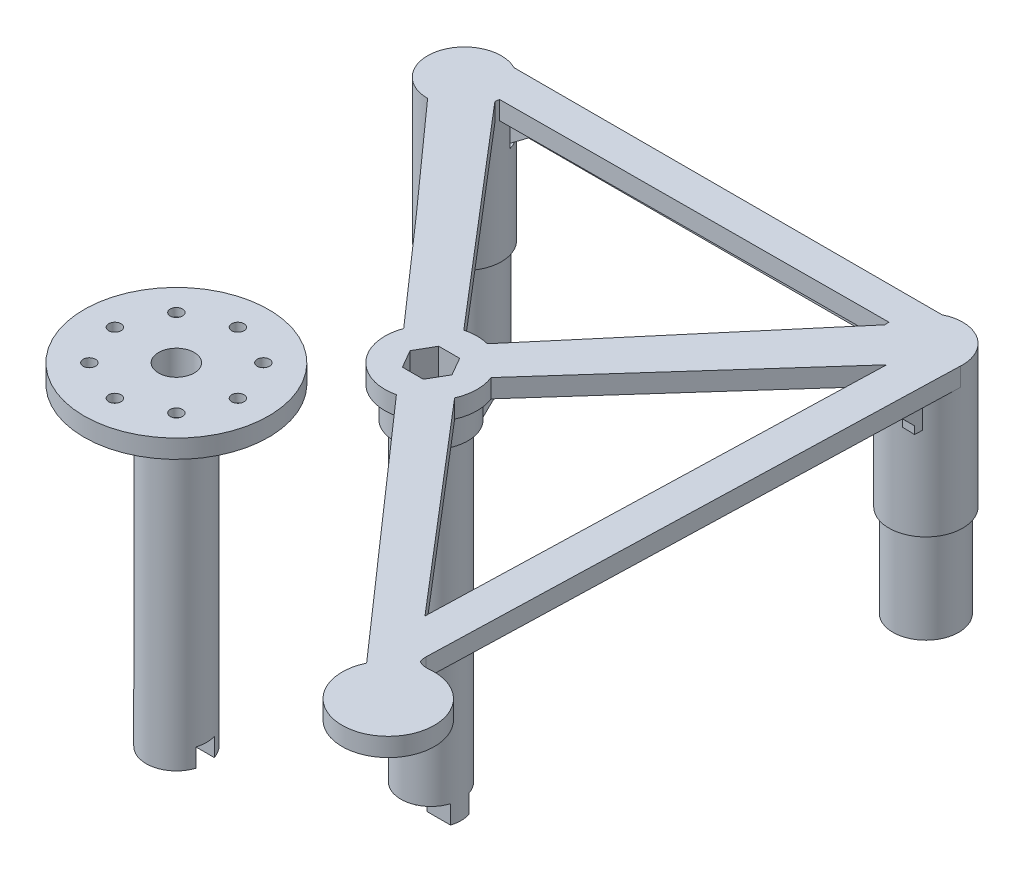
SolidWorks part; units mm, degrees
ref_plane "前视基准面" through (0, 0, 0) normal (0, 0, 1) x (1, 0, 0)
ref_plane "上视基准面" through (0, 0, 0) normal (0, 1, 0) x (1, 0, 0)
ref_plane "右视基准面" through (0, 0, 0) normal (1, 0, 0) x (0, 0, -1)
sketch "草图1" plane through (0, 0, 0) normal (0, 1, 0) x (1, 0, 0)
  line L1 (-18.6554, 0) -> (18.8446, -42.931)
  line L2 (18.8446, -42.931) -> (56.3446, 0)
  line L3 (-18.6554, 0) -> (56.3446, 0)
  dimension "D4" = 75
extrude "凸台-拉伸1" add sketch "草图1" along normal blind 3
sketch "草图2" plane through (0, 3, 0) normal (0, 1, 0) x (1, 0, 0)
  circle A0 centre (56.3446, 0) radius 5.35
  circle A1 centre (-18.6554, 0) radius 5.35
  dimension "D1" = 10.7
  dimension "D2" = 10.7
extrude "凸台-拉伸2" add sketch "草图2" against normal blind 23
sketch "草图3" plane through (0, 0, 0) normal (0, -1, 0) x (1, 0, 0)
  line L6 (8.6327, 17.5594) -> (1.1561, 9)
  line L7 (1.1561, 9) -> (33.7591, 9)
  line L8 (8.6327, 17.5594) -> (18.8446, 29.2503)
  line L9 (18.8446, 29.2503) -> (29.0566, 17.5594)
  line L10 (29.0566, 17.5594) -> (36.5332, 9)
  line L11 (36.5332, 9) -> (33.7591, 9)
  dimension "D4" = 26.8879
  dimension "D5" = 26.8879
  dimension "D6" = 35.3771
extrude "切除-拉伸1" cut sketch "草图3" against normal blind 3
sketch "草图4" plane through (0, 0, 0) normal (0, -1, 0) x (1, 0, 0)
  circle A0 centre (18.8446, 42.931) radius 5
  dimension "D1" = 10
extrude "凸台-拉伸3" add sketch "草图4" along normal blind 100
sketch "草图5" plane through (0, 0, 0) normal (0, 1, 0) x (1, 0, 0)
  circle A0 centre (18.8446, -42.931) radius 5
extrude "凸台-拉伸4" add sketch "草图5" along normal blind 3
sketch "草图6" plane through (0, -20, 0) normal (0, -1, 0) x (1, 0, 0)
  circle A0 centre (56.3446, 0) radius 5.35
extrude "凸台-拉伸5" add sketch "草图6" along normal blind 5
sketch "草图7" plane through (0, -20, 0) normal (0, -1, 0) x (1, 0, 0)
  circle A0 centre (-18.6554, 0) radius 5.35
extrude "凸台-拉伸6" add sketch "草图7" along normal blind 5
sketch "草图8" plane through (0, 3, 0) normal (0, 1, 0) x (1, 0, 0)
  line L0 (-18.6554, 5.35) -> (56.3446, 5.35)
  line L1 (56.3446, 5.35) -> (56.3446, -5.35)
  line L2 (56.3446, -5.35) -> (-18.6554, -5.35)
  line L3 (-18.6554, -5.35) -> (-18.6554, 5.35)
  arc A1 (52.8251, -4.0293) -> (50.9946, 0) centre (56.3446, 0) ccw construction
  arc A2 (-13.3054, 0) -> (-15.1358, -4.0293) centre (-18.6554, 0) ccw construction
  circle A3 centre (-18.6554, 0) radius 5.35 construction
extrude "凸台-拉伸7" add sketch "草图8" against normal blind 3
sketch "草图9" plane through (0, 3, 0) normal (0, 1, 0) x (1, 0, 0)
  line L0 (61.6946, 0) -> (18.8446, -47.931)
  line L1 (18.8446, -47.931) -> (-24.0054, 0)
  line L2 (-24.0054, 0) -> (61.6946, 0)
  arc A0 (56.3446, -5.35) -> (56.3446, 5.35) centre (56.3446, 0) ccw construction
  arc A1 (15.5553, -39.1653) -> (22.134, -39.1653) centre (18.8446, -42.931) ccw construction
  arc A2 (-18.6554, 5.35) -> (-18.6554, -5.35) centre (-18.6554, 0) ccw construction
extrude "凸台-拉伸8" add sketch "草图9" against normal blind 3
sketch "草图10" plane through (0, 0, 0) normal (0, -1, 0) x (1, 0, 0)
  line L0 (18.8446, 37.931) -> (-13.3137, 0.299)
  line L1 (-13.3137, 0.299) -> (50.9946, 0)
  line L2 (50.9946, 0) -> (18.8446, 37.931)
  arc A0 (13.8759, 42.373) -> (23.8134, 42.373) centre (18.8446, 42.931) ccw construction
  arc A1 (-18.6554, -5.35) -> (-19.2524, 5.3166) centre (-18.6554, 0) ccw construction
  circle A2 centre (56.3446, 0) radius 5.35 construction
  arc A3 (56.9416, 5.3166) -> (56.3446, -5.35) centre (56.3446, 0) ccw construction
extrude "切除-拉伸2" cut sketch "草图10" against normal blind 3
sketch "草图12" plane through (0, 3, 0) normal (0, 1, 0) x (1, 0, 0)
  circle A0 centre (-18.6554, 0) radius 6
  circle A1 centre (56.3446, 0) radius 6
  dimension "D1" = 12
  dimension "D2" = 12
extrude "凸台-拉伸10" add sketch "草图12" against normal blind 13
sketch "草图13" plane through (0, -25, 0) normal (0, -1, 0) x (1, 0, 0)
  circle A0 centre (-18.6554, 0) radius 3
  circle A1 centre (56.3446, 0) radius 3
  dimension "D1" = 6
  dimension "D2" = 6
extrude "切除-拉伸3" cut sketch "草图13" against normal blind 23
sketch "草图14" plane through (0, -100, 0) normal (0, -1, 0) x (1, 0, 0)
  circle A0 centre (18.8446, 42.931) radius 3.125
  dimension "D1" = 6.25
extrude "切除-拉伸5" cut sketch "草图14" against normal blind 100
sketch "草图15" plane through (0, -10, 0) normal (0, -1, 0) x (1, 0, 0)
  circle A0 centre (56.3446, 0) radius 5.35
  circle A1 centre (56.3446, 0) radius 6
extrude "凸台-拉伸11" add sketch "草图15" along normal blind 5
sketch "草图16" plane through (0, -10, 0) normal (0, -1, 0) x (1, 0, 0)
  circle A0 centre (-18.6554, 0) radius 3
  circle A1 centre (-18.6554, 0) radius 6
extrude "凸台-拉伸12" add sketch "草图16" along normal blind 5
sketch "草图17" plane through (0, -25, 0) normal (0, -1, 0) x (1, 0, 0)
  circle A0 centre (-18.6554, 0) radius 3
  circle A1 centre (-18.6554, 0) radius 5.35
extrude "凸台-拉伸13" add sketch "草图17" along normal blind 5
sketch "草图18" plane through (0, -25, 0) normal (0, -1, 0) x (1, 0, 0)
  circle A0 centre (56.3446, 0) radius 3
  circle A1 centre (56.3446, 0) radius 5.35
extrude "凸台-拉伸14" add sketch "草图18" along normal blind 5
sketch "草图20" plane through (0, -15, 0) normal (0, -1, 0) x (1, 0, 0)
  circle A0 centre (-18.6554, 0) radius 5.35
  circle A1 centre (-18.6554, 0) radius 6
extrude "凸台-拉伸15" add sketch "草图20" along normal blind 5
sketch "草图21" plane through (0, -15, 0) normal (0, -1, 0) x (1, 0, 0)
  circle A0 centre (56.3446, 0) radius 5.35
  circle A1 centre (56.3446, 0) radius 6
extrude "凸台-拉伸16" add sketch "草图21" along normal blind 5
sketch "草图22" plane through (0, -30, 0) normal (0, -1, 0) x (1, 0, 0)
  circle A0 centre (-18.6554, 0) radius 3
  circle A1 centre (-18.6554, 0) radius 5.35
extrude "凸台-拉伸17" add sketch "草图22" along normal blind 5
sketch "草图23" plane through (0, -30, 0) normal (0, -1, 0) x (1, 0, 0)
  circle A0 centre (56.3446, 0) radius 3
  circle A1 centre (56.3446, 0) radius 5.35
extrude "凸台-拉伸18" add sketch "草图23" along normal blind 5
sketch "草图25" plane through (0, 3, 0) normal (0, 1, 0) x (1, 0, 0)
  circle A0 centre (18.8446, -42.931) radius 7.5
  dimension "D1" = 15
extrude "凸台-拉伸20" add sketch "草图25" against normal blind 3
sketch "草图28" plane through (0, 3, 0) normal (0, 1, 0) x (1, 0, 0)
  line L1 (-3.3796, -23.0714) -> (2.0936, -18.3287)
  line L2 (-3.3796, -23.0714) -> (64.3216, -100.0268)
  line L3 (64.3216, -100.0268) -> (66.8686, -97.9101)
  line L4 (-18.6414, -6) -> (11.8821, -40.1429) construction
  line L5 (2.0936, -18.3287) -> (68.6526, -96.2167)
  line L6 (16.9224, -35.6815) -> (-12.7353, -0.9759) construction
  line L7 (68.6526, -96.2167) -> (66.8686, -97.9101)
extrude "凸台-拉伸21" add sketch "草图28" against normal blind 3
sketch "草图29" plane through (0, 3, 0) normal (0, 1, 0) x (1, 0, 0)
  line L0 (56.3446, 0) -> (53.7411, -88)
  line L1 (20.5226, -50.2409) -> (64.3216, -100.0268) construction
  line L2 (53.7411, -88) -> (59.7411, -88)
  line L3 (56.3446, 0) -> (62.3446, 0)
  line L4 (62.3446, 0) -> (59.7411, -88)
  arc A1 (56.3307, -6) -> (53.6285, 5.35) centre (56.3446, 0) ccw construction
  dimension "D2" = 6
  dimension "D3" = 88
extrude "凸台-拉伸23" add sketch "草图29" against normal blind 3
sketch "草图30" plane through (0, 3, 0) normal (0, 1, 0) x (1, 0, 0)
  circle A0 centre (62.6532, -93.6946) radius 7.5
  dimension "D1" = 15
extrude "凸台-拉伸24" add sketch "草图30" against normal blind 3
fillet "圆角1" radius 3 2 edges at (60.3876, 1.5, 86.545) (59.8043, 1.5, 85.8624)
sketch "草图31" plane through (0, 0, 0) normal (0, -1, 0) x (1, 0, 0)
  line L0 (-14.7236, -1.6282) -> (-14.7236, -3.6282)
  line L1 (-14.7236, -3.6282) -> (53.5274, -3.6282)
  line L2 (53.5274, -3.6282) -> (53.8249, -1.6282)
  line L3 (53.8249, -1.6282) -> (-14.7236, -1.6282)
  line L4 (49.6098, 80.1025) -> (51.1303, 78.8032)
  line L5 (22.3188, 45.0877) -> (51.1303, 78.8032)
  line L6 (49.6098, 80.1025) -> (20.7983, 46.387)
  line L7 (-15.3496, 4.0864) -> (-13.8291, 2.7871)
  line L8 (20.3259, 39.1868) -> (51.8689, 1.9719)
  line L9 (20.3259, 39.1868) -> (21.8516, 40.4799)
  line L10 (51.8689, 1.9719) -> (53.3946, 3.265)
  line L11 (21.8516, 40.4799) -> (53.3946, 3.265)
  line L12 (20.7983, 46.387) -> (22.3188, 45.0877)
  line L13 (15.5768, 40.2768) -> (17.0973, 38.9775)
  line L14 (17.0973, 38.9775) -> (-13.8291, 2.7871)
  line L15 (-15.3496, 4.0864) -> (15.5768, 40.2768)
  line L16 (56.0939, 78.8643) -> (58.3189, 3.6596)
  line L17 (58.3189, 3.6596) -> (60.3198, 3.6596)
  line L18 (60.3198, 3.6596) -> (58.093, 78.9234)
  line L19 (58.093, 78.9234) -> (56.0939, 78.8643)
  circle A0 centre (-18.6554, 0) radius 5.35 construction
  circle A1 centre (56.3446, 0) radius 3 construction
  dimension "D1" = 2
  dimension "D2" = 2
  dimension "D3" = 2
  dimension "D4" = 2
  dimension "D5" = 2
extrude "凸台-拉伸29" add sketch "草图31" along normal blind 5
sketch "草图35" plane through (0, 0, -3.6282) normal (0, 0, -1) x (-1, 0, 0)
  line L0 (13.8766, -5) -> (9.8766, -2)
  line L1 (9.8766, -2) -> (-47.5659, -2)
  line L2 (-47.5659, -2) -> (-51.5659, -5)
  line L3 (-51.5659, -5) -> (13.8766, -5)
  line L4 (13.8766, 0) -> (-51.5659, 0) construction
  dimension "D1" = 2
  dimension "D2" = 4
  dimension "D3" = 4
sketch "草图36" plane through (0, -5, 0) normal (0, -1, 0) x (1, 0, 0)
  line L0 (18.8446, -3.6282) -> (18.8446, -1.6282)
  line L1 (-9.8766, -3.6282) -> (47.5659, -3.6282) construction
  line L2 (50.5698, -1.6282) -> (-12.8805, -1.6282) construction
sweep "切除-扫描1" cut profiles "草图35" path "草图36"
sketch "草图37" plane through (60.3752, 0, 1.7863) normal (0.9996, 0, 0.0296) x (0.0296, 0, -0.9996)
  line L0 (-2.7315, -5) -> (-6.7315, -1)
  line L1 (-6.7315, -1) -> (-73.1709, -1)
  line L2 (-73.1709, -1) -> (-77.1709, -5)
  line L3 (-77.1709, -5) -> (-2.7315, -5)
  line L5 (-82.8983, 0) -> (1.4889, 0) construction
  dimension "D1" = 1
  dimension "D2" = 4
  dimension "D3" = 4
sketch "草图38" plane through (0, -5, 0) normal (0, -1, 0) x (1, 0, 0)
  line L0 (59.1937, 41.72) -> (57.1928, 41.72)
  line L1 (60.1761, 8.5148) -> (58.2113, 74.9252) construction
  line L2 (56.0939, 78.8643) -> (58.2589, 5.6864) construction
sweep "切除-扫描3" cut profiles "草图37" path "草图38"
sketch "草图39" plane through (58.3761, 0, 1.7271) normal (0.9996, 0, 0.0296) x (0.0296, 0, -0.9996)
  line L0 (-3.961, -3.8296) -> (-3.961, -5)
  line L1 (-3.961, -5) -> (-2.7315, -5)
  line L2 (-3.961, -3.8296) -> (-3.961, -3.2722)
  line L3 (-3.961, -3.2722) -> (-2.7315, -4.5017)
  line L4 (-2.7315, 0) -> (-2.7315, -5) construction
  line L5 (-2.7315, -4.5017) -> (-2.7315, -5)
extrude "凸台-拉伸31" add sketch "草图39" along normal blind 2
sketch "草图40" plane through (-10.8895, 0, 9.3056) normal (-0.7602, 0, 0.6497) x (0.6497, 0, 0.7602)
  line L0 (-5.1212, -5) -> (-3.1212, -1)
  line L2 (39.938, -5) -> (-6.1212, -5) construction
  line L3 (-3.1212, -1) -> (36.938, -1)
  line L5 (36.938, -1) -> (38.938, -5)
  line L6 (38.938, -5) -> (-5.1212, -5)
  line L7 (39.938, 0) -> (-6.1212, 0) construction
  dimension "D1" = 1
  dimension "D2" = 2
  dimension "D3" = 1
  dimension "D4" = 1
  dimension "D5" = 2
sketch "草图42" plane through (0, -5, 0) normal (0, -1, 0) x (1, 0, 0)
  line L0 (0.0951, 22.1599) -> (1.5521, 20.7864)
  line L1 (-12.9172, 6.9328) -> (13.1074, 37.387) construction
  line L2 (-13.5363, 3.1298) -> (16.6406, 38.443) construction
sweep "切除-扫描5" cut profiles "草图40" path "草图42"
sketch "草图43" plane through (31.1568, 0, 26.4083) normal (-0.7628, 0, -0.6466) x (-0.6466, 0, 0.7628)
  line L0 (14.7346, -5) -> (12.7346, -1)
  line L1 (15.7346, -5) -> (-30.8257, -5) construction
  line L2 (12.7346, -1) -> (-27.8257, -1)
  line L3 (-27.8257, -1) -> (-29.8257, -5)
  line L4 (14.7346, -5) -> (-29.8257, -5)
  line L5 (15.7346, 0) -> (-30.8257, 0) construction
  dimension "D1" = 1
  dimension "D2" = 1
  dimension "D3" = 1
  dimension "D4" = 2
  dimension "D5" = 2
sketch "草图44" plane through (0, -5, 0) normal (0, -1, 0) x (1, 0, 0)
  line L0 (36.0357, 20.6522) -> (37.4729, 22.0498)
  line L1 (22.9229, 36.1228) -> (49.1484, 5.1816) construction
  line L2 (52.36, 4.4858) -> (22.5858, 39.6138) construction
sweep "切除-扫描6" cut profiles "草图43" path "草图44"
sketch "草图46" plane through (-10.8895, 0, 9.3056) normal (-0.7602, 0, 0.6497) x (0.6497, 0, 0.7602)
  line L0 (50.8218, -5) -> (52.8218, -1)
  line L1 (93.1256, -5) -> (49.8218, -5) construction
  line L2 (52.8218, -1) -> (88.1256, -1)
  line L3 (88.1256, -1) -> (93.1256, 0)
  line L4 (93.1256, 0) -> (93.1256, -5)
  line L5 (93.1256, -5) -> (50.8218, -5)
  line L6 (93.1256, 0) -> (49.8218, 0) construction
  dimension "D1" = 1
  dimension "D2" = 1
  dimension "D3" = 2
  dimension "D4" = 5
sketch "草图47" plane through (0, -5, 0) normal (0, -1, 0) x (1, 0, 0)
  line L0 (37.0322, 62.3055) -> (35.5118, 63.6048)
  line L1 (22.9341, 45.8078) -> (51.1303, 78.8032) construction
  line L2 (23.4264, 49.4624) -> (46.3616, 76.3014) construction
sweep "切除-扫描7" cut profiles "草图46" path "草图47"
sketch "草图48" plane through (60.3752, 0, 1.7863) normal (0.9996, 0, 0.0296) x (0.0296, 0, -0.9996)
  line L0 (-73.1709, -1) -> (-77.1709, 0)
  line L1 (-77.1709, 0) -> (-77.1709, -5)
  line L2 (-73.1709, -1) -> (-77.1709, -5)
sketch "草图49" plane through (0, -1, 0) normal (0, -1, 0) x (1, 0, 0)
  line L0 (58.2113, 74.9252) -> (56.2104, 74.9252)
  line L1 (56.2104, 74.9252) -> (55.38, 74.9252)
sweep "切除-扫描8" cut profiles "草图48" path "草图49"
sketch "草图50" plane through (0, 3, 0) normal (0, 1, 0) x (1, 0, 0)
  circle A0 centre (18.8446, -42.931) radius 5.9982
extrude "凸台-拉伸32" add sketch "草图50" against normal blind 103
sketch "草图52" plane through (0, -100, 0) normal (0, -1, 0) x (1, 0, 0)
  circle A0 centre (18.8446, 42.931) radius 5.9982
  circle A1 centre (18.8446, 42.931) radius 4.9
  dimension "D1" = 9.8
extrude "切除-拉伸7" cut sketch "草图52" against normal blind 95
sketch "草图53" plane through (0, -100, 0) normal (0, -1, 0) x (1, 0, 0)
  circle A0 centre (18.8446, 42.931) radius 4.9
extrude "切除-拉伸8" cut sketch "草图53" against normal blind 44
sketch "草图54" plane through (0, -56, 0) normal (0, -1, 0) x (1, 0, 0)
  line L1 (22.0201, 42.931) -> (20.4324, 45.681)
  line L2 (20.4324, 45.681) -> (17.2569, 45.681)
  line L3 (17.2569, 45.681) -> (15.6692, 42.931)
  line L4 (15.6692, 42.931) -> (17.2569, 40.181)
  line L5 (17.2569, 40.181) -> (20.4324, 40.181)
  line L6 (20.4324, 40.181) -> (22.0201, 42.931)
  circle A0 centre (18.8446, 42.931) radius 1.5
  circle A1 centre (18.8446, 42.931) radius 2.75 construction
  dimension "D1" = 3
  dimension "D2" = 5.5
extrude "凸台-拉伸33" add sketch "草图54" along normal blind 5
sketch "草图55" plane through (0, 3, 0) normal (0, 1, 0) x (1, 0, 0)
  line L1 (22.0778, -42.931) -> (20.4612, -40.131)
  line L2 (20.4612, -40.131) -> (17.2281, -40.131)
  line L3 (17.2281, -40.131) -> (15.6115, -42.931)
  line L4 (15.6115, -42.931) -> (17.2281, -45.731)
  line L5 (17.2281, -45.731) -> (20.4612, -45.731)
  line L6 (20.4612, -45.731) -> (22.0778, -42.931)
  circle A0 centre (18.8446, -42.931) radius 2.8 construction
  dimension "D1" = 5.6
extrude "切除-拉伸9" cut sketch "草图55" against normal blind 56
sketch "草图56" plane through (0, -56, 0) normal (0, -1, 0) x (1, 0, 0)
  circle A0 centre (18.8446, 42.931) radius 1.5
extrude "切除-拉伸10" cut sketch "草图56" against normal blind 6
sketch "草图57" plane through (0, 0, 0) normal (0, 1, 0) x (1, 0, 0)
  circle A1 centre (-1.8509, -63.6265) radius 15
  dimension "D1" = 30
extrude "凸台-拉伸34" add sketch "草图57" along normal blind 3 separate body
sketch "草图58" plane through (0, 0, 0) normal (0, -1, 0) x (1, 0, 0)
  circle A0 centre (-1.8509, 63.6265) radius 4.9
  dimension "D1" = 9.8
extrude "凸台-拉伸35" add sketch "草图58" along normal blind 51
sketch "草图59" plane through (0, -51, 0) normal (0, -1, 0) x (1, 0, 0)
  line L1 (1.3246, 63.6265) -> (-0.2631, 66.3765)
  line L2 (-0.2631, 66.3765) -> (-3.4386, 66.3765)
  line L3 (-3.4386, 66.3765) -> (-5.0263, 63.6265)
  line L4 (-5.0263, 63.6265) -> (-3.4386, 60.8765)
  line L5 (-3.4386, 60.8765) -> (-0.2631, 60.8765)
  line L6 (-0.2631, 60.8765) -> (1.3246, 63.6265)
  circle A0 centre (-1.8509, 63.6265) radius 2.75 construction
  dimension "D1" = 5.5
extrude "切除-拉伸11" cut sketch "草图59" against normal blind 5
sketch "草图60" plane through (0, 3, 0) normal (0, 1, 0) x (1, 0, 0)
  circle A0 centre (-1.8509, -63.6265) radius 2.75
  dimension "D1" = 5.5
extrude "切除-拉伸12" cut sketch "草图60" against normal blind 46
sketch "草图61" plane through (0, -46, 0) normal (0, -1, 0) x (1, 0, 0)
  circle A0 centre (-1.8509, 63.6265) radius 1.5
  dimension "D1" = 3
extrude "切除-拉伸13" cut sketch "草图61" against normal blind 9
sketch "草图62" plane through (0, 0, 0) normal (0, -1, 0) x (1, 0, 0)
  line L4 (10.5163, 63.6265) -> (9.3327, 65.6765)
  line L5 (9.3327, 65.6765) -> (6.9656, 65.6765)
  line L6 (6.9656, 65.6765) -> (5.782, 63.6265)
  line L7 (5.782, 63.6265) -> (6.9656, 61.5765)
  line L8 (6.9656, 61.5765) -> (9.3327, 61.5765)
  line L9 (9.3327, 61.5765) -> (10.5163, 63.6265)
  circle A1 centre (8.1491, 63.6265) radius 2.05 construction
  dimension "D2" = 4.1
extrude "切除-拉伸14" cut sketch "草图62" against normal blind 1.65
sketch "草图63" plane through (0, 1.65, 0) normal (0, -1, 0) x (1, 0, 0)
  circle A0 centre (8.1491, 63.6265) radius 1
  dimension "D1" = 2
extrude "切除-拉伸15" cut sketch "草图63" against normal blind 1.5
pattern_circular "阵列(圆周)1" count 8 over 360 about axis through (-1.8509, -51, 63.6265) along (0, 1, 0) of "切除-拉伸14", "切除-拉伸15"
sketch "草图64" plane through (0, -61, 0) normal (0, -1, 0) x (1, 0, 0)
  circle A0 centre (18.8446, 42.931) radius 3.1754
extrude "切除-拉伸17" cut sketch "草图64" against normal blind 5
sketch "草图65" plane through (0, 3, 0) normal (0, 1, 0) x (1, 0, 0)
  line L1 (22.251, -42.931) -> (20.5478, -39.981)
  line L2 (20.5478, -39.981) -> (17.1415, -39.981)
  line L3 (17.1415, -39.981) -> (15.4383, -42.931)
  line L4 (15.4383, -42.931) -> (17.1415, -45.881)
  line L5 (17.1415, -45.881) -> (20.5478, -45.881)
  line L6 (20.5478, -45.881) -> (22.251, -42.931)
  circle A0 centre (18.8446, -42.931) radius 2.95 construction
  dimension "D1" = 5.9
extrude "切除-拉伸18" cut sketch "草图65" against normal blind 56
fillet "圆角2" radius 1 6 edges at (16.2899, -53, 41.456) (16.2899, -53, 44.406) (18.8446, -53, 45.881) (21.3994, -53, 44.406) (21.3994, -53, 41.456) (18.8446, -53, 39.981)
sketch "草图66" plane through (0, -51, 0) normal (0, -1, 0) x (1, 0, 0)
  line L1 (1.3246, 63.6265) -> (-0.2631, 66.3765)
  line L2 (-0.2631, 66.3765) -> (-3.4386, 66.3765)
  line L3 (-3.4386, 66.3765) -> (-5.0263, 63.6265)
  line L4 (-5.0263, 63.6265) -> (-3.4386, 60.8765)
  line L5 (-3.4386, 60.8765) -> (-0.2631, 60.8765)
  line L6 (-0.2631, 60.8765) -> (1.3246, 63.6265)
  circle A0 centre (-1.8509, 63.6265) radius 2.75 construction
extrude "凸台-拉伸36" add sketch "草图66" against normal blind 5
sketch "草图67" plane through (0, -51, 0) normal (0, -1, 0) x (1, 0, 0)
  circle A0 centre (-1.8509, 63.6265) radius 1.5
extrude "切除-拉伸19" cut sketch "草图67" against normal blind 5
fillet "圆角3" radius 1 1 edges at (-1.8509, -43, 66.3765)
sketch "草图68" plane through (0, -56, 0) normal (0, -1, 0) x (1, 0, 0)
  line L0 (17.9735, 41.4222) -> (13.9446, 41.431)
  line L2 (19.7158, 41.4222) -> (23.7446, 41.431)
  line L3 (13.9446, 44.431) -> (17.9735, 44.4398)
  line L4 (13.9446, 44.431) -> (15.6975, 48.0373)
  line L5 (19.7158, 44.4398) -> (23.7446, 44.431)
  line L6 (15.6975, 48.0373) -> (21.9917, 48.0373)
  line L7 (21.9917, 48.0373) -> (23.7446, 44.431)
  line L8 (23.7446, 41.431) -> (21.6473, 37.6278)
  line L9 (21.6473, 37.6278) -> (15.8637, 37.534)
  line L10 (20.5869, 42.931) -> (19.7158, 44.4398)
  line L11 (15.8637, 37.534) -> (13.9446, 41.431)
  line L12 (17.9735, 44.4398) -> (17.1024, 42.931)
  line L13 (17.1024, 42.931) -> (17.9735, 41.4222)
  line L15 (19.7158, 41.4222) -> (20.5869, 42.931)
  line L21 (17.9735, 41.4222) -> (19.7158, 41.4222) [skipped]
  line L22 (19.7158, 44.4398) -> (17.9735, 44.4398) [skipped]
  circle A3 centre (18.8446, 42.931) radius 1.5088 construction
  arc A4 (23.3281, 46.9155) -> (15.1566, 38.2006) centre (18.8446, 42.931) ccw construction
  arc A5 (22.1322, 47.948) -> (14.4015, 38.9014) centre (18.8446, 42.931) ccw construction
sketch "草图69" plane through (0, -56, 0) normal (0, -1, 0) x (1, 0, 0)
  circle A0 centre (18.8446, 42.931) radius 4.9
extrude "凸台-拉伸37" add sketch "草图69" along normal blind 3
extrude "切除-拉伸20" cut sketch "草图68" along normal blind 3
sketch "草图70" plane through (0, -51, 0) normal (0, -1, 0) x (1, 0, 0)
  line L0 (-2.7169, 65.1265) -> (-0.9848, 65.1265)
  line L1 (-0.9848, 65.1265) -> (3.2201, 65.1265)
  line L3 (-0.9848, 62.1265) -> (-2.7169, 62.1265)
  line L8 (3.2201, 65.1265) -> (3.2201, 62.1265)
  line L9 (3.2201, 62.1265) -> (-0.9848, 62.1265)
  line L10 (-2.7169, 62.1265) -> (-7.4797, 62.1265)
  line L11 (-7.4797, 62.1265) -> (-7.4797, 65.1265)
  line L12 (-7.4797, 65.1265) -> (-2.7169, 65.1265)
extrude "切除-拉伸21" cut sketch "草图70" against normal blind 3
sketch "草图71" plane through (0, 3, 0) normal (0, 1, 0) x (1, 0, 0)
  circle A0 centre (-1.8509, -63.6265) radius 2.9
  dimension "D1" = 5.8
extrude "切除-拉伸22" cut sketch "草图71" against normal blind 46
fillet "圆角4" radius 1 1 edges at (-1.8509, -43, 66.5265)
sketch "草图72" plane through (0, -56, 0) normal (0, -1, 0) x (1, 0, 0)
  circle A0 centre (18.8446, 42.931) radius 1.7422
extrude "切除-拉伸23" cut sketch "草图72" along normal blind 3
